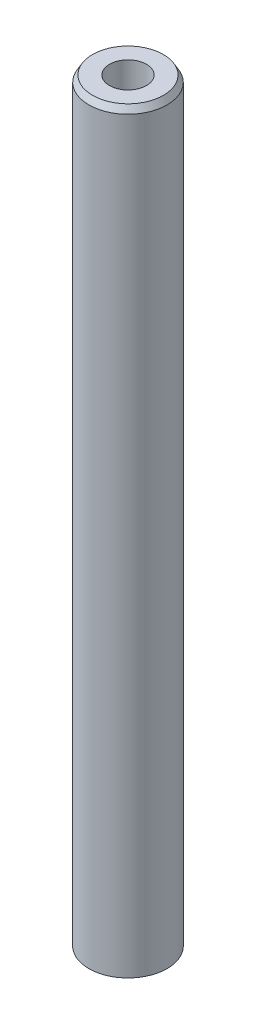
SolidWorks part; units mm, degrees
ref_plane "Front Plane" through (0, 0, 0) normal (0, 0, 1) x (1, 0, 0)
ref_plane "Top Plane" through (0, 0, 0) normal (0, 1, 0) x (1, 0, 0)
ref_plane "Right Plane" through (0, 0, 0) normal (1, 0, 0) x (0, 0, -1)
sketch "Sketch1" plane through (0, 0, 0) normal (0, 1, 0) x (1, 0, 0)
  circle A0 centre (0, 0) radius 5
  dimension "SHAFT_OD" = 10
extrude "Boss-Extrude1" add sketch "Sketch1" along normal blind 96.8892
sketch "Sketch2" plane through (0, 0, 0) normal (0, 1, 0) x (1, 0, 0)
  circle A0 centre (0, 0) radius 2.3628
  dimension "BORE_D" = 4.7255
extrude "Cut-Extrude1" cut sketch "Sketch2" along normal through all
chamfer "Chamfer1" distance 0.8207 angle 30 2 edges at (0, 96.8892, 5) (0, 0, 5) first distance on face at (0, 96.8892, 5) first distance on face at (0, 0, 2.3628)
